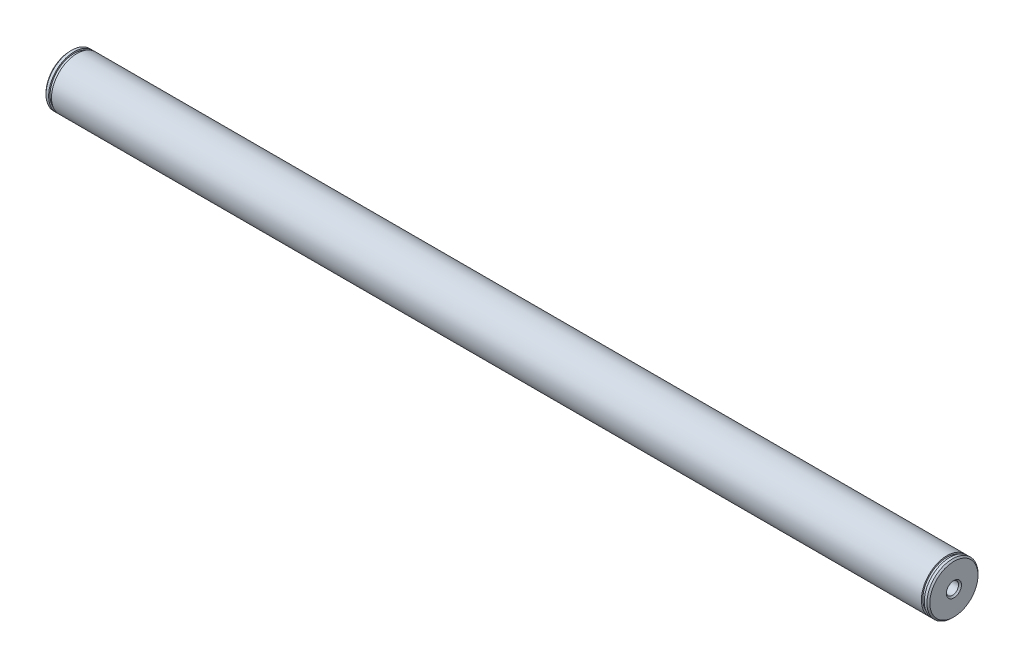
SolidWorks part; units mm, degrees
ref_plane "Front" through (0, 0, 0) normal (0, 0, 1) x (1, 0, 0)
ref_plane "Top" through (0, 0, 0) normal (0, 1, 0) x (1, 0, 0)
ref_plane "Right" through (0, 0, 0) normal (1, 0, 0) x (0, 0, -1)
sketch "Sketch1" plane through (0, 0, 0) normal (1, 0, 0) x (0, 0, -1)
  circle A0 centre (0, 0) radius 11.176
  dimension "D1" = 22.352
extrude "Boss-Extrude1" add sketch "Sketch1" along normal mid plane 386.715
sketch "Sketch2" plane through (-193.3575, 0, 0) normal (-1, 0, 0) x (0, 0, 1)
  circle A0 centre (0, 0) radius 10.541
  dimension "D1" = 21.082
extrude "Cut-Extrude1" cut sketch "Sketch2" against normal blind 1.27 from offset 1.778 flip side to cut offset against normal yes
sketch "Sketch3" plane through (-193.3575, 0, 0) normal (-1, 0, 0) x (0, 0, 1)
  circle A0 centre (0, 0) radius 2.667
  dimension "D1" = 5.334
extrude "Cut-Extrude2" cut sketch "Sketch3" against normal blind 25.4
mirror "Mirror1" about plane through (0, 0, 0) normal (1, 0, 0) of "Cut-Extrude2", "Cut-Extrude1"
chamfer "Chamfer1" distance 0.635 angle 45 4 edges at (-193.3575, 0, -11.176) (-193.3575, 0, 2.667) (193.3575, 0, -11.176) (193.3575, 0, 2.667)
